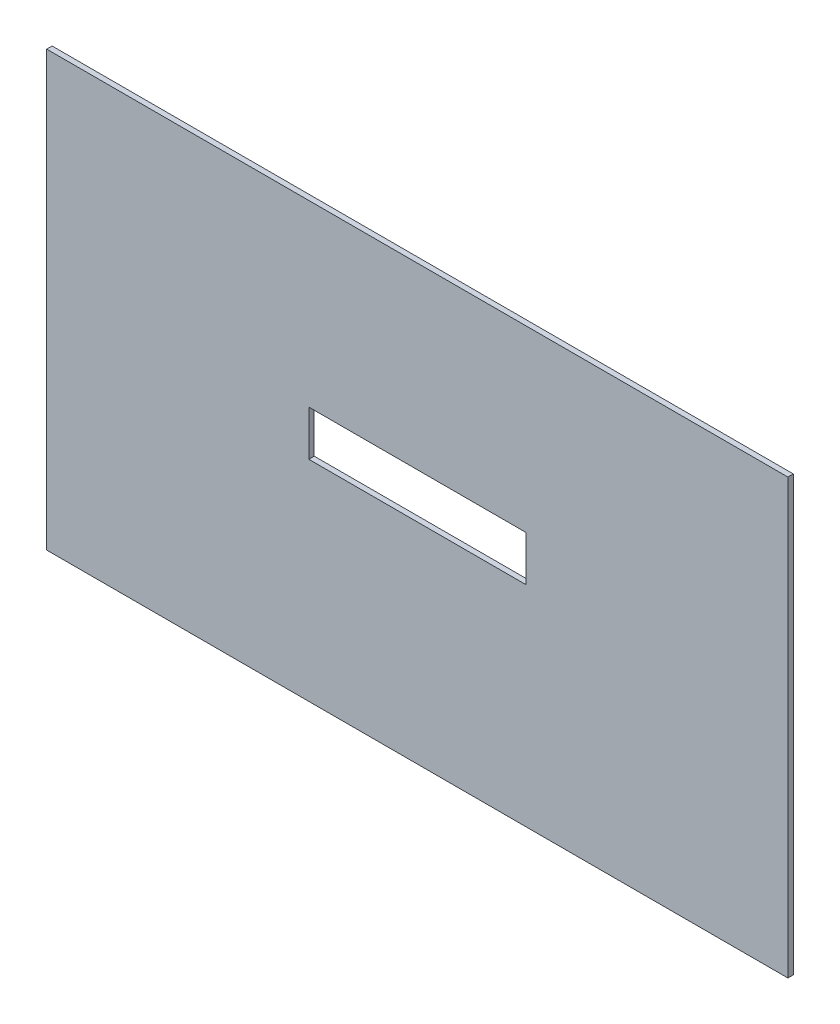
SolidWorks part; units mm, degrees
material "Acrylic (Medium-high impact)"
ref_plane "Front Plane" through (0, 0, 0) normal (0, 0, 1) x (1, 0, 0)
ref_plane "Top Plane" through (0, 0, 0) normal (0, 1, 0) x (1, 0, 0)
ref_plane "Right Plane" through (0, 0, 0) normal (1, 0, 0) x (0, 0, -1)
sketch "Sketch1" plane through (0, 0, 0) normal (0, 0, 1) x (1, 0, 0)
  line L1 (-205, -120) -> (205, -120)
  line L2 (-205, -120) -> (-205, 120)
  line L3 (-205, 120) -> (205, 120)
  line L4 (205, -120) -> (205, 120)
  line L5 (-205, -120) -> (205, 120) construction
  line L6 (-205, 120) -> (205, -120) construction
  point P0 (0, 0)
  dimension "D1" = 240
  dimension "D2" = 410
extrude "Boss-Extrude1" add sketch "Sketch1" along normal mid plane 3
sketch "Sketch2" plane through (0, 0, 1.5) normal (0, 0, 1) x (1, 0, 0)
  line L0 (-205, -120) -> (205, -120) construction
  line L1 (-60, -4) -> (60, -4)
  line L2 (-60, -4) -> (-60, 21)
  line L3 (-60, 21) -> (60, 21)
  line L4 (60, -4) -> (60, 21)
  line L5 (-60, -4) -> (60, 21) construction
  line L6 (-60, 21) -> (60, -4) construction
  point P0 (0, 8.5)
  point P7 (2.7696, 8.2223)
  dimension "D1" = 120
  dimension "D2" = 116
  dimension "D3" = 25
extrude "Cut-Extrude1" cut sketch "Sketch2" against normal through all
